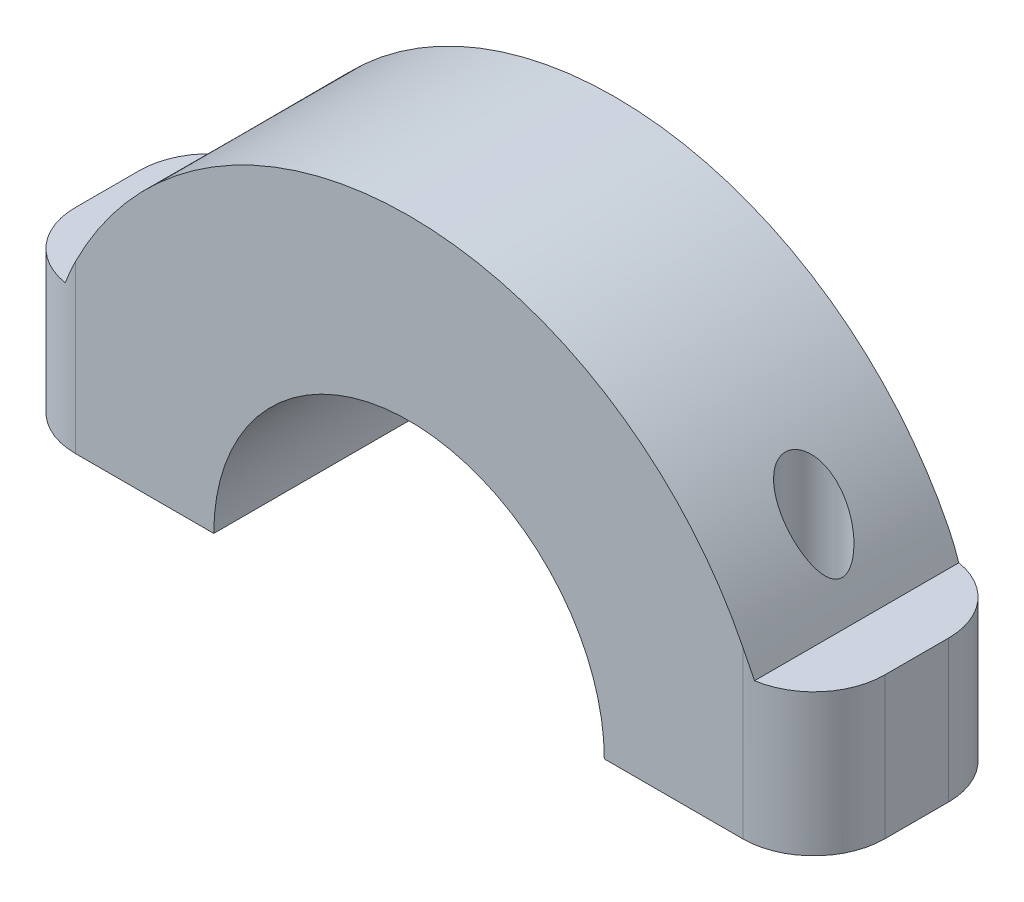
SolidWorks part; units mm, degrees
ref_plane "Front Plane" through (0, 0, 0) normal (0, 0, 1) x (1, 0, 0)
ref_plane "Top Plane" through (0, 0, 0) normal (0, 1, 0) x (1, 0, 0)
ref_plane "Right Plane" through (0, 0, 0) normal (1, 0, 0) x (0, 0, -1)
sketch "Sketch1" plane through (0, 0, 0) normal (0, 1, 0) x (1, 0, 0)
  line L0 (-11.4, 2.9) -> (-5.5, 2.9)
  line L1 (-11.5, 3) -> (-5.5, 3) construction
  line L2 (-11.5, 3) -> (-11.5, -3) construction
  line L3 (-11.5, -3) -> (-5.5, -3) construction
  line L4 (-5.5, 2.9) -> (-5.5, -2.9)
  line L5 (-5.6, 2.9) -> (-5.6, -2.9) construction
  line L6 (-11.4, -2.9) -> (-5.5, -2.9)
  line L7 (-11.4, 2.9) -> (-11.4, -2.9)
  line L8 (-11.4, -2.9) -> (-5.6, -2.9) construction
  line L9 (-11.4, 2.9) -> (-5.6, 2.9) construction
  line L10 (-5.5, 3) -> (-5.5, -3) construction
  point P4 (-5.5, 0)
  dimension "D1" = 6
  dimension "D2" = 6
  dimension "D3" = 5.5
  dimension "D4" = 0.1
extrude "Boss-Extrude1" add sketch "Sketch1" along normal blind 4
sketch "Sketch2" plane through (0, 0, 2.9) normal (0, 0, 1) x (1, 0, 0)
  line L0 (-10.5, 0) -> (-5.5, 0)
  line L1 (5.5, 0) -> (10.5, 0)
  arc A0 (5.5, 0) -> (-5.5, 0) centre (0, 0) ccw
  arc A1 (10.5, 0) -> (-10.5, 0) centre (0, 0) ccw
  dimension "D1" = 5
extrude "Boss-Extrude2" add sketch "Sketch2" against normal up to surface (5.8 mm away) up to face at (-8.45, 2, -2.9)
mirror "Mirror3" about plane through (0, 0, 0) normal (1, 0, 0) of bodies 102 101
combine bodies "Combine1" operation type add bodies to combine 102 103
fillet "Fillet1" radius 2 4 edges at (-11.4, 2, -2.9) (-11.4, 2, 2.9) (11.4, 2, -2.9) (11.4, 2, 2.9)
hole_wizard "M2x0.4 Tapped Hole1" positions "Sketch5" profile "Sketch4" tap size "M2x0.4" standard "ANSI Metric" end condition through all
sketch "Sketch5" plane through (0, 0, 0) normal (0, -1, 0) x (-1, 0, 0)
  line L0 (8.5, 2.9) -> (8.5, -2.9) construction
  line L4 (5.5, 0) -> (11.5, 0) construction
  line L5 (5.5, -2.9) -> (5.5, 2.9) construction
  line L8 (0, 3.19) -> (0, -3.19) construction
  line L9 (9.4, -2.9) -> (5.5, -2.9) construction
  line L10 (5.5, 2.9) -> (9.4, 2.9) construction
  line L11 (11.4, 0.9) -> (11.4, -0.9) construction
  point P21 (8.5, 0)
  point P25 (-8.5, 0)
  dimension "D1" = 0.1
sketch "Sketch4" plane through (8.5, 0, 0) normal (1, 0, 0) x (0, 0, -1)
  line L0 (0, 0) -> (0, 10.5)
  line L1 (0, 10.5) -> (0.8, 10.5)
  line L2 (0.8, 10.5) -> (0.8, 0)
  line L5 (0.8, 0) -> (0, 0)
  line L11 (0, -6.35) -> (0, 107.95) construction
  dimension "Thru Tap Drill Dia." = 1.6
  dimension "Thru Tap Drill Depth" = 10.5
sketch "Sketch6" plane through (0, 4, 0) normal (0, 1, 0) x (1, 0, 0)
  line L0 (0, -3.19) -> (0, 3.19) construction
  line L1 (9.7269, 2.125) -> (7.2731, 2.125)
  line L2 (7.2731, 2.125) -> (6.0463, 0)
  line L3 (6.0463, 0) -> (7.2731, -2.125)
  line L4 (7.2731, -2.125) -> (9.7269, -2.125)
  line L5 (9.7269, -2.125) -> (10.9537, 0)
  line L6 (10.9537, 0) -> (9.7269, 2.125)
  line L7 (-10.9537, 0) -> (-9.7269, 2.125)
  line L8 (-9.7269, -2.125) -> (-10.9537, 0)
  line L9 (-7.2731, -2.125) -> (-9.7269, -2.125)
  line L10 (-6.0463, 0) -> (-7.2731, -2.125)
  line L11 (-7.2731, 2.125) -> (-6.0463, 0)
  line L12 (-9.7269, 2.125) -> (-7.2731, 2.125)
  circle A0 centre (8.5, 0) radius 2.125 construction
  circle A1 centre (-8.5, 0) radius 2.125 construction
  dimension "D1" = 4.25
extrude "Cut-Extrude1" [suppressed] cut sketch "Sketch6" along normal up to surface (7.9545 mm away)
